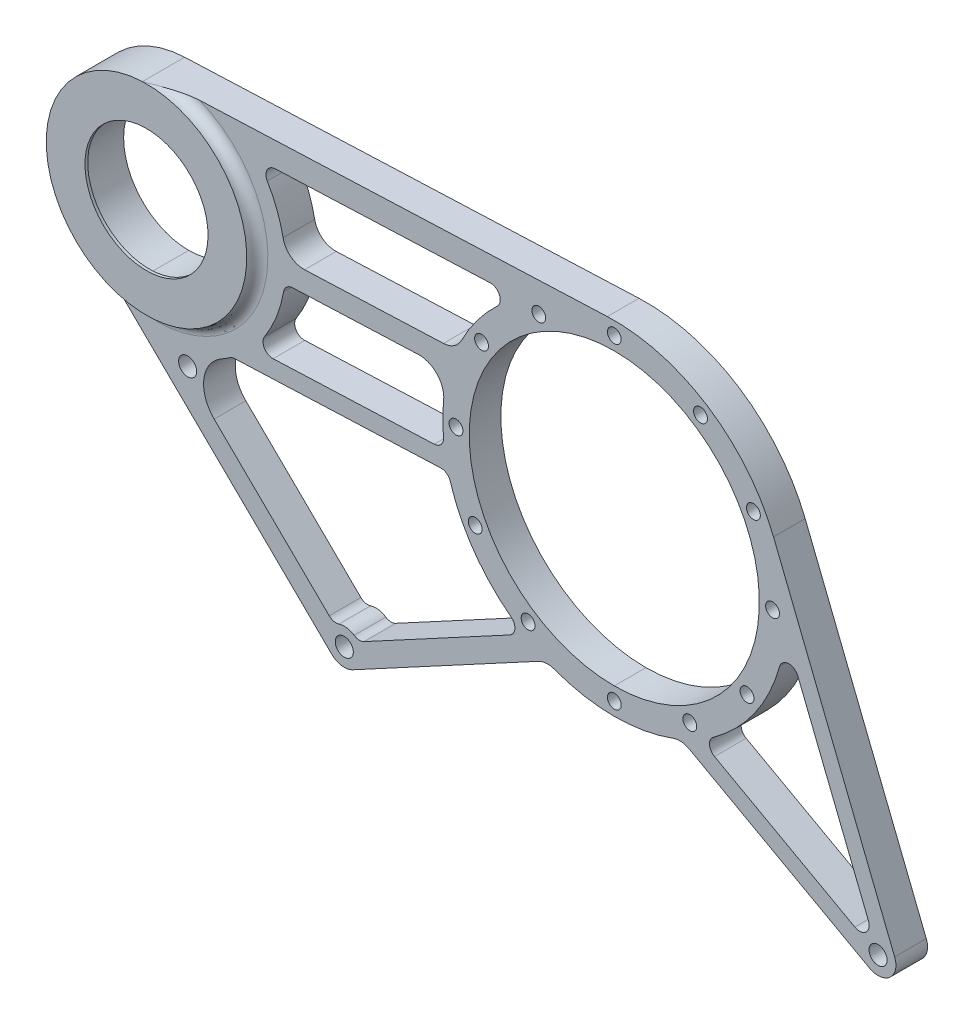
SolidWorks part; units mm, degrees
material "6061-T6 (SS)"
ref_plane "Front Plane" through (0, 0, 0) normal (0, 0, 1) x (1, 0, 0)
ref_plane "Top Plane" through (0, 0, 0) normal (0, 1, 0) x (1, 0, 0)
ref_plane "Right Plane" through (0, 0, 0) normal (1, 0, 0) x (0, 0, -1)
sketch "Sketch1" plane through (0, 0, 0) normal (0, 0, 1) x (1, 0, 0)
  line L0 (-114.3, 95.25) -> (-114.3, 107.95) construction
  line L1 (-280.8642, 163.1704) -> (-116.8043, 169.8118)
  line L2 (-304.7421, 101.1501) -> (-216.3071, 14.4521)
  line L3 (-13.0706, 21.4387) -> (-56.8054, 130.918)
  line L4 (-208.742, 13.3833) -> (-141.7118, 49.5504)
  line L5 (-22.1639, 13.4141) -> (-87.2342, 49.3665)
  circle A0 centre (-279.4, 127) radius 23.5
  circle A1 centre (-114.3, 95.25) radius 36 construction
  circle A2 centre (0, 0) radius 12.7 construction
  circle A3 centre (-228.6, 0) radius 12.7 construction
  circle A4 centre (-114.3, 107.95) radius 52.3875
  circle A5 centre (-19.05, 19.05) radius 3.2639
  circle A6 centre (-211.7995, 19.05) radius 3.2639
  circle A7 centre (-279.4, 127) radius 36.2
  arc A8 (-135.9521, 49.947) -> (-93.0137, 49.8118) centre (-114.3, 107.95) ccw
  arc A9 (-216.3071, 14.4521) -> (-208.742, 13.3833) centre (-211.7995, 19.05) ccw
  arc A10 (-22.1639, 13.4141) -> (-13.0706, 21.4387) centre (-19.05, 19.05) ccw
  arc A11 (-56.8054, 130.918) -> (-116.8043, 169.8118) centre (-114.3, 107.95) ccw
  arc A12 (-135.9521, 49.947) -> (-141.7118, 49.5504) centre (-138.3949, 43.4031) ccw
  arc A13 (-87.2342, 49.3665) -> (-93.0137, 49.8118) centre (-90.6122, 43.2526) ccw
  dimension "D5" = 72
  dimension "D6" = 47
  dimension "D7" = 25.4
  dimension "D8" = 25.4
  dimension "D11" = 104.775
  dimension "D14" = 6.5278
  dimension "D15" = 6.5278
  dimension "D16" = 25.4
  dimension "D17" = 12.7
  dimension "D18" = 123.825
  dimension "D19" = 3.175
  dimension "D20" = 6.985
  dimension "D21" = 6.985
  dimension "D1" = 114.3
  dimension "D2" = 95.25
  dimension "D3" = 279.4
  dimension "D4" = 127
  dimension "D9" = 228.6
  dimension "D10" = 12.7
  dimension "D12" = 19.05
  dimension "D13" = 19.05
extrude "Boss-Extrude1" add sketch "Sketch1" along normal blind 11.43 contours A13 L5 A10 L3 A11 L1 A7 L2 A9 L4 A12 A8 A6 A5 A4 | A7 A0 region at (-168.693, 91.0379, 0) region at (-255.035, 152.3713, 0)
sketch "Sketch2" plane through (0, 0, 11.43) normal (0, 0, 1) x (1, 0, 0)
  circle A0 centre (-279.4, 127) radius 36.2
  circle A1 centre (-279.4, 127) radius 23.5
extrude "Boss-Extrude2" add sketch "Sketch2" along normal blind 3.81
fillet "Fillet1" radius 3.81 1 edges at (-245.6173, 113.9936, 11.43)
sketch "Sketch3" plane through (0, 0, 11.43) normal (0, 0, 1) x (1, 0, 0)
  line L0 (-114.3, 107.95) -> (-114.3, 165.1) construction
  line L1 (-114.3, 107.95) -> (-57.15, 107.95) construction
  line L2 (-114.3, 107.95) -> (-83.1739, 155.88) construction
  line L3 (-114.3, 107.95) -> (-64.0756, 135.2196) construction
  circle A0 centre (-114.3, 107.95) radius 57.15 construction
  circle A11 centre (-114.3, 165.1) radius 2.5
  circle A12 centre (-57.15, 107.95) radius 2.5
  circle A13 centre (-114.3, 50.8) radius 2.5
  circle A14 centre (-171.45, 107.95) radius 2.5
  circle A15 centre (-83.1739, 155.88) radius 2.5
  circle A16 centre (-64.0756, 135.2196) radius 2.5
  circle A17 centre (-66.37, 76.8239) radius 2.5
  circle A18 centre (-87.0304, 57.7256) radius 2.5
  circle A19 centre (-145.4261, 60.02) radius 2.5
  circle A20 centre (-164.5244, 80.6804) radius 2.5
  circle A21 centre (-162.23, 139.0761) radius 2.5
  circle A22 centre (-141.5696, 158.1744) radius 2.5
  point P14 (-114.3, 107.95)
  point P25 (-114.3, 107.95)
  point P33 (-114.3, 107.95)
  dimension "D1" = 114.3
  dimension "D2" = 5
  dimension "D6" = 5
  dimension "D4" = 33
  dimension "D5" = 61.5
  dimension "D3" = 4
  dimension "D7" = 4
extrude "5mm Holes" cut sketch "Sketch3" against normal through all
sketch "Sketch4" plane through (0, 0, 15.24) normal (0, 0, 1) x (1, 0, 0)
  circle A0 centre (-279.4, 127) radius 22.225
  circle A1 centre (-279.4, 127) radius 23.5 construction
  circle A2 centre (-279.4, 127) radius 23.5
  dimension "D1" = 44.45
extrude "Boss-Extrude3" add sketch "Sketch4" against normal blind 1
sketch "Sketch5" plane through (0, 0, 11.43) normal (0, 0, 1) x (1, 0, 0)
  line L0 (-48.0193, 91.8071) -> (-22.5033, 27.9342)
  line L1 (-13.0706, 21.4387) -> (-56.8054, 130.918) construction
  line L2 (-78.1047, 51.5771) -> (-27.4356, 23.5816)
  line L3 (-22.1639, 13.4141) -> (-87.2342, 49.3665) construction
  line L4 (-236.7455, 156.0591) -> (-159.125, 159.2013)
  line L5 (-263.8382, 163.8596) -> (-116.8043, 169.8118) construction
  line L6 (-226.1253, 129.7972) -> (-175.9845, 131.827)
  line L7 (-230.4174, 121.9972) -> (-185.1154, 123.8311)
  line L8 (-258.7869, 66.7686) -> (-217.2302, 26.028)
  line L9 (-204.6483, 24.2506) -> (-152.0143, 52.6499)
  line L10 (-292.5742, 89.2212) -> (-216.3071, 14.4521) construction
  line L11 (-208.742, 13.3833) -> (-141.7118, 49.5504) construction
  line L12 (-237.4937, 96.2899) -> (-179.3047, 98.6455)
  line L13 (-251.3498, 89.3738) -> (-177.0086, 92.3833)
  arc A0 (-175.0426, 119.9291) -> (-175.9673, 102.4457) centre (-114.3, 107.95) ccw construction
  circle A1 centre (-211.7995, 19.05) radius 6.4389 construction
  circle A2 centre (-19.05, 19.05) radius 6.4389 construction
  arc A3 (-54.6287, 91.4427) -> (-78.4387, 57.481) centre (-114.3, 107.95) cw
  arc A4 (-48.0193, 91.8071) -> (-54.6287, 91.4427) centre (-51.2626, 90.5115) ccw
  arc A5 (-27.4356, 23.5816) -> (-22.5033, 27.9342) centre (-25.7466, 26.6385) ccw
  arc A6 (-78.1047, 51.5771) -> (-78.4387, 57.481) centre (-76.4157, 54.634) cw
  arc A7 (-233.9104, 135.9413) -> (-239.6024, 150.7781) centre (-279.4, 127) ccw construction
  arc A8 (-292.5742, 89.2212) -> (-263.8382, 163.8596) centre (-279.4, 127) ccw construction
  arc A9 (-213.7352, 25.191) -> (-208.2383, 24.4145) centre (-211.7995, 19.05) cw
  arc A10 (-156.5977, 153.1613) -> (-169.499, 135.9897) centre (-114.3, 107.95) ccw
  arc A11 (-175.9093, 114.0697) -> (-175.9673, 102.4457) centre (-114.3, 107.95) ccw
  arc A12 (-173.5263, 89.9112) -> (-151.5703, 58.5123) centre (-114.3, 107.95) ccw
  arc A13 (-239.6024, 150.7781) -> (-233.9104, 135.9413) centre (-279.4, 127) cw
  arc A14 (-233.7176, 119.1025) -> (-240.5609, 101.6865) centre (-279.4, 127) cw
  arc A15 (-240.5609, 101.6865) -> (-233.7176, 119.1025) centre (-279.4, 127) ccw construction
  arc A16 (-253.1835, 88.7646) -> (-256.2406, 86.8392) centre (-279.4, 127) cw
  arc A17 (-159.125, 159.2013) -> (-156.5977, 153.1613) centre (-158.9837, 155.7117) cw
  arc A20 (-236.7455, 156.0591) -> (-239.6024, 150.7781) centre (-236.6043, 152.5695) ccw
  arc A21 (-179.3047, 98.6455) -> (-175.9673, 102.4457) centre (-179.446, 102.1352) ccw
  arc A23 (-230.4174, 121.9972) -> (-233.7176, 119.1025) centre (-230.2762, 118.5075) ccw
  arc A24 (-237.4937, 96.2899) -> (-240.5609, 101.6865) centre (-237.6349, 99.7796) cw
  arc A25 (-217.2302, 26.028) -> (-213.7352, 25.191) centre (-214.7852, 28.522) ccw
  arc A26 (-204.6483, 24.2506) -> (-208.2383, 24.4145) centre (-206.3067, 27.3242) cw
  arc A27 (-152.0143, 52.6499) -> (-151.5703, 58.5123) centre (-153.6727, 55.7236) ccw
  arc A28 (-177.0086, 92.3833) -> (-173.5263, 89.9112) centre (-176.8673, 88.8936) cw
  arc A29 (-251.3498, 89.3738) -> (-253.1835, 88.7646) centre (-251.2085, 85.8842) ccw
  arc A31 (-173.5263, 89.9112) -> (-170.4887, 133.9499) centre (-114.3, 107.95) ccw construction
  arc A32 (-273.3418, 81.0375) -> (-253.1835, 88.7646) centre (-279.4, 127) ccw construction
  arc A33 (-258.7869, 66.7686) -> (-256.2406, 86.8392) centre (-249.8962, 75.8374) cw
  arc A34 (-169.499, 135.9897) -> (-175.9845, 131.827) centre (-176.2928, 139.4407) cw
  arc A35 (-233.9104, 135.9413) -> (-226.1253, 129.7972) centre (-226.4335, 137.411) ccw
  arc A36 (-185.1154, 123.8311) -> (-175.9093, 114.0697) centre (-184.7558, 114.9484) cw
  point P17 (-52.5701, 103.1988)
  point P23 (-83.2204, 54.4036)
  point P51 (-148.3837, 159.6362)
  point P54 (-171.3442, 132.0148)
  point P60 (-243.0732, 155.8029)
  point P63 (-175.5324, 98.7982)
  point P66 (-174.02, 124.2803)
  point P75 (-215.4925, 24.3245)
  point P78 (-206.7898, 23.0951)
  point P81 (-146.981, 55.3657)
  point P84 (-174.2524, 92.4948)
  point P90 (-273.3418, 81.0375)
  dimension "D1" = 123.825
  dimension "D2" = 12.8778
  dimension "D5" = 3.4925
  dimension "D6" = 6.35
  dimension "D14" = 3.4925
  dimension "D15" = 12.7
  dimension "D16" = 7.62
  dimension "D17" = 7.62
  dimension "D18" = 8.89
  dimension "D3" = 6.35
  dimension "D4" = 6.35
  dimension "D7" = 8.89
  dimension "D8" = 7.62
  dimension "D9" = 7.62
  dimension "D10" = 7.62
  dimension "D11" = 6.35
  dimension "D12" = 25.4
  dimension "D13" = 26.67
extrude "Cut-Extrude2" cut sketch "Sketch5" against normal through all both and the other way through all
ref_axis "Axis2" through (-279.4, 127, 14.24) along (0, 0, -1)
ref_axis "Axis1" through (-114.3, 107.95, 11.43) along (0, 0, -1)
ref_plane "Plane1" through (-114.3, 0, 0) normal (1, 0, 0) x (0, 0, -1)
ref_plane "Plane2" through (-279.4, 0, 0) normal (1, 0, 0) x (0, 0, -1)
ref_plane "Plane3" through (0, 0, 5.715) normal (0, 0, -1) x (-1, 0, 0)
ref_plane "Plane4" through (0, 0, 7.12) normal (0, 0, -1) x (-1, 0, 0)
split line "Split Line1"
split line "Split Line2"
sketch "Sketch6" plane through (0, 0, 5.715) normal (0, 0, -1) x (-1, 0, 0)
  circle A1 centre (114.3, 107.95) radius 52.3875 construction
sketch "Sketch7" plane through (0, 0, 7.12) normal (0, 0, -1) x (-1, 0, 0)
  circle A0 centre (279.4, 127) radius 23.5
sketch "Sketch8" plane through (0, 0, 11.43) normal (0, 0, 1) x (1, 0, 0)
  circle A0 centre (-268.3542, 78.4783) radius 3.2639
extrude "Cut-Extrude3" cut sketch "Sketch8" against normal through all both and the other way through all
ref_point "Puck Center"
ref_point "Bearing Center"
sketch "Sketch9" plane through (0, 0, 0) normal (0, 0, 1) x (1, 0, 0)
  line L0 (-210.8988, 25.4256) -> (-210.8988, 91.0113) construction
  line L1 (-177.0086, 92.3833) -> (-251.3498, 89.3738) construction
  line L2 (-236.1159, 143.6054) -> (-163.7987, 145.1392) construction
  circle A0 centre (-114.3, 107.95) radius 31.75 construction
  arc A1 (-208.2383, 24.4145) -> (-213.7352, 25.191) centre (-211.7995, 19.05) ccw construction
  circle A2 centre (-210.8988, 77.2346) radius 5.08
  circle A3 centre (-210.8988, 45.0623) radius 5.08
  circle A4 centre (-146.05, 107.95) radius 5.08
  circle A5 centre (-114.3, 139.7) radius 5.08
  circle A6 centre (-82.55, 107.95) radius 5.08
  circle A7 centre (-114.3, 76.2) radius 5.08
  arc A8 (-233.9104, 135.9413) -> (-239.6024, 150.7781) centre (-279.4, 127) ccw construction
  arc A9 (-156.5977, 153.1613) -> (-169.499, 135.9897) centre (-114.3, 107.95) ccw construction
  circle A10 centre (-199.9573, 144.3723) radius 5.08
  point P0 (-48.5383, 56.2255)
  point P8 (-146.05, 107.95)
  point P30 (-114.3, 107.95)
  dimension "D1" = 63.5
  dimension "D2" = 10.16
  dimension "D3" = 10.16
  dimension "D4" = 10.16
  dimension "D6" = 10.16
  dimension "D5" = 4
sketch "Sketch10" plane through (0, 0, 0) normal (0, 0, -1) x (-1, 0, 0)
  line L0 (202.0088, 77.2346) -> (202.0088, 45.0623)
  line L1 (219.7888, 77.2346) -> (219.7888, 45.0623)
  circle A0 centre (114.3, 107.95) radius 38.1
  circle A1 centre (199.9573, 144.3723) radius 8.89
  circle A2 centre (199.9573, 144.3723) radius 5.08
  circle A3 centre (199.9573, 144.3723) radius 5.08 construction
  circle A4 centre (146.05, 107.95) radius 5.08
  circle A5 centre (146.05, 107.95) radius 5.08 construction
  circle A6 centre (210.8988, 45.0623) radius 5.08
  circle A7 centre (210.8988, 45.0623) radius 5.08 construction
  circle A8 centre (210.8988, 77.2346) radius 5.08
  circle A9 centre (210.8988, 77.2346) radius 5.08 construction
  circle A10 centre (114.3, 76.2) radius 5.08
  circle A11 centre (114.3, 76.2) radius 5.08 construction
  circle A12 centre (82.55, 107.95) radius 5.08
  circle A13 centre (82.55, 107.95) radius 5.08 construction
  circle A14 centre (114.3, 139.7) radius 5.08
  circle A15 centre (114.3, 139.7) radius 5.08 construction
  arc A16 (219.7888, 77.2346) -> (202.0088, 77.2346) centre (210.8988, 77.2346) ccw
  arc A17 (202.0088, 45.0623) -> (219.7888, 45.0623) centre (210.8988, 45.0623) ccw
  circle A18 centre (210.8988, 45.0623) radius 8.89 construction
  circle A19 centre (210.8988, 77.2346) radius 8.89 construction
  dimension "D1" = 76.2
  dimension "D9" = 3.81
  dimension "D2" = 0
  dimension "D3" = 0
  dimension "D4" = 0
  dimension "D5" = 0
  dimension "D6" = 0
  dimension "D7" = 0
  dimension "D8" = 0
  dimension "D10" = 3.81
